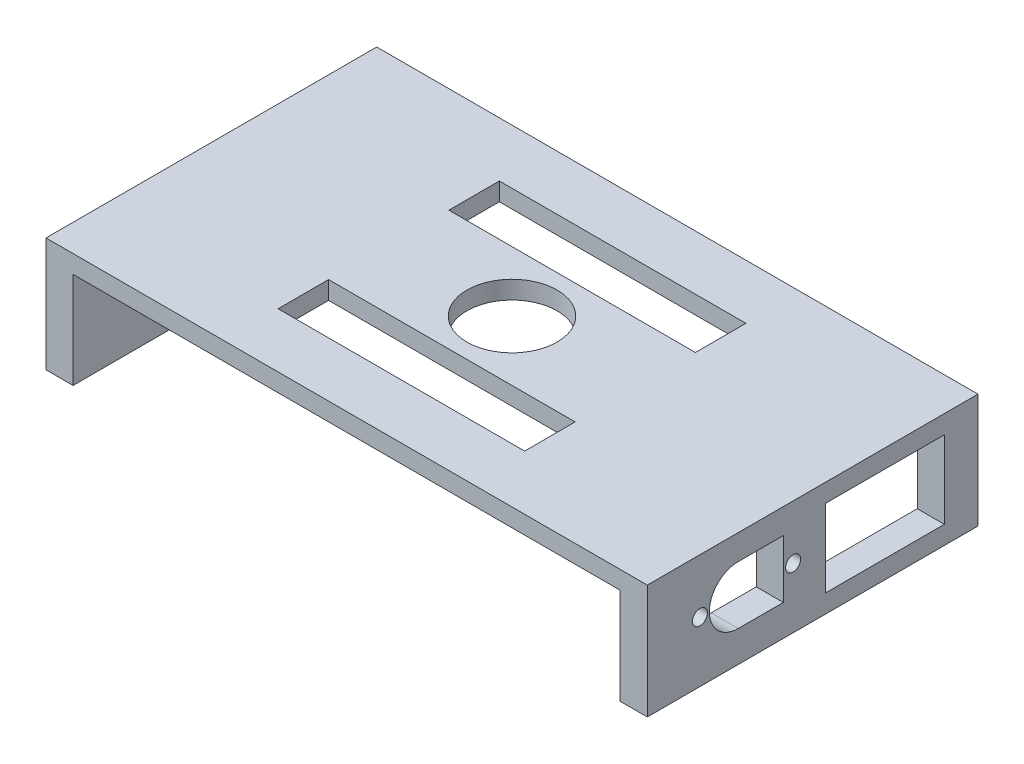
SolidWorks part; units mm, degrees
ref_plane "Front Plane" through (0, 0, 0) normal (0, 0, 1) x (1, 0, 0)
ref_plane "Top Plane" through (0, 0, 0) normal (0, 1, 0) x (1, 0, 0)
ref_plane "Right Plane" through (0, 0, 0) normal (1, 0, 0) x (0, 0, -1)
sketch "Sketch1" plane through (0, 0, 0) normal (0, 1, 0) x (1, 0, 0)
  line L1 (-50, -27.5) -> (50, -27.5)
  line L2 (-50, -27.5) -> (-50, 27.5)
  line L3 (-50, 27.5) -> (50, 27.5)
  line L4 (50, -27.5) -> (50, 27.5)
  line L5 (-50, -27.5) -> (50, 27.5) construction
  line L6 (-50, 27.5) -> (50, -27.5) construction
  point P0 (0, 0)
  dimension "D1" = 100
  dimension "D2" = 55
extrude "Boss-Extrude1" add sketch "Sketch1" along normal blind 19
sketch "Sketch2" plane through (0, 0, 0) normal (0, -1, 0) x (1, 0, 0)
  line L1 (-45.5, -45.5) -> (45.5, -45.5)
  line L2 (-45.5, -45.5) -> (-45.5, 45.5)
  line L3 (-45.5, 45.5) -> (45.5, 45.5)
  line L4 (45.5, -45.5) -> (45.5, 45.5)
  line L5 (-45.5, -45.5) -> (45.5, 45.5) construction
  line L6 (-45.5, 45.5) -> (45.5, -45.5) construction
  point P0 (0, 0)
  dimension "D1" = 91
  dimension "D2" = 91
extrude "Cut-Extrude1" cut sketch "Sketch2" against normal blind 16
sketch "Sketch3" plane through (50, 0, 0) normal (1, 0, 0) x (0, 0, -1)
  line L3 (-4.8718, 5.185) -> (-4.8718, 14.815)
  line L4 (-4.8718, 5.185) -> (-12.3679, 5.185)
  line L9 (-4.8718, 14.815) -> (-12.3679, 14.815)
  arc A1 (-12.3679, 5.185) -> (-12.3679, 14.815) centre (-12.3679, 10) cw
  circle A2 centre (-18.75, 10) radius 1.25
  circle A3 centre (-3.25, 10) radius 1.25
  point P17 (-11, 10)
extrude "Cut-Extrude3" cut sketch "Sketch3" against normal up to next
sketch "Sketch15" plane through (50, 0, 0) normal (1, 0, 0) x (0, 0, -1)
  line L0 (0, 0) -> (0, 19) construction
  line L1 (-27.5, 19) -> (27.5, 19) construction
  line L2 (0, 9.5) -> (12, 9.5) construction
  line L4 (2.1, 3.05) -> (21.9, 3.05)
  line L5 (2.1, 3.05) -> (2.1, 15.95)
  line L6 (2.1, 15.95) -> (21.9, 15.95)
  line L7 (21.9, 3.05) -> (21.9, 15.95)
  line L8 (2.1, 3.05) -> (21.9, 15.95) construction
  line L9 (2.1, 15.95) -> (21.9, 3.05) construction
  dimension "D1" = 12
  dimension "D2" = 19.8
  dimension "D3" = 12.9
extrude "Cut-Extrude13" cut sketch "Sketch15" against normal up to next
sketch "Sketch6" plane through (0, 19, 0) normal (0, 1, 0) x (1, 0, 0)
  line L0 (0, 0) -> (0, -10) construction
  line L1 (20.5, -10) -> (-20.5, -10)
  line L2 (-20.5, -10) -> (-20.5, -18.4)
  line L3 (20.5, -10) -> (20.5, -18.4)
  line L4 (20.5, -18.4) -> (-20.5, -18.4)
  line L5 (0, 0) -> (5, 0) construction
  line L6 (20.5, 10) -> (20.5, 18.4)
  line L7 (20.5, 10) -> (-20.5, 10)
  line L8 (-20.5, 10) -> (-20.5, 18.4)
  line L9 (20.5, 18.4) -> (-20.5, 18.4)
  circle A0 centre (0, 0) radius 7.5
  point P6 (0, -10)
  dimension "D5" = 15
  dimension "D1" = 10
  dimension "D2" = 41
  dimension "D3" = 8.4
  dimension "D4" = 5
extrude "Cut-Extrude14" cut sketch "Sketch6" against normal up to next
